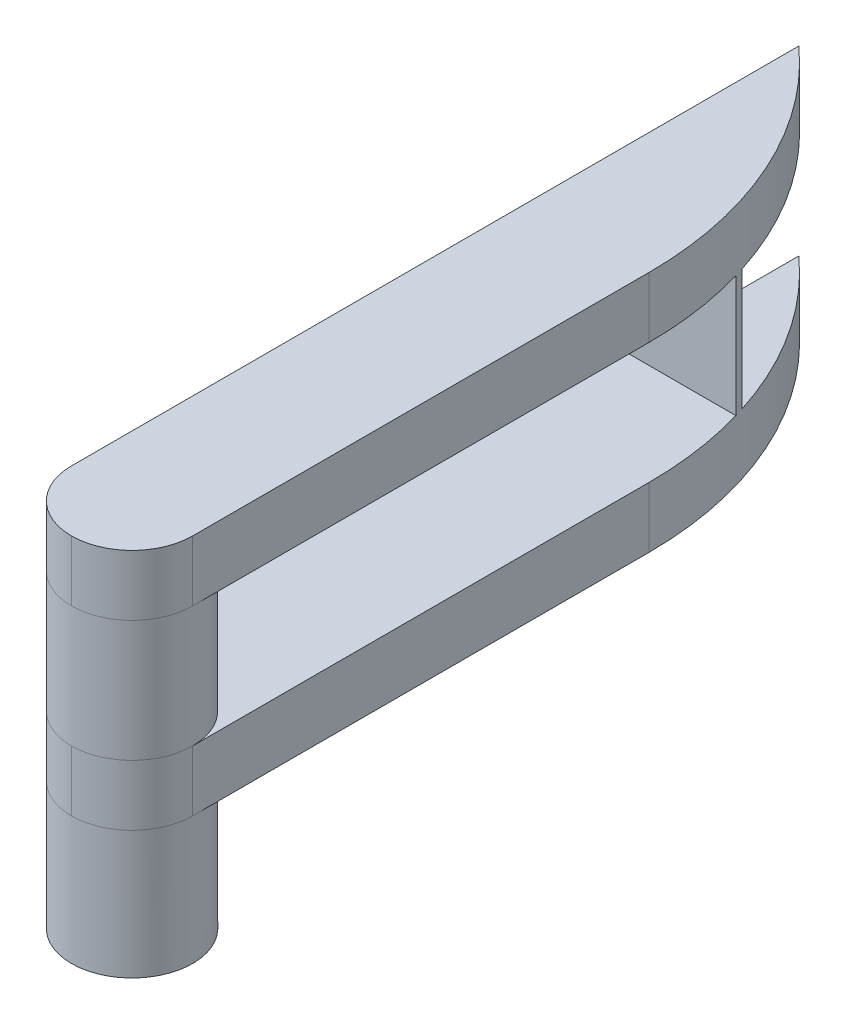
SolidWorks part; units mm, degrees
ref_plane "Plan de face" through (0, 0, 0) normal (0, 0, 1) x (1, 0, 0)
ref_plane "Plan de dessus" through (0, 0, 0) normal (0, 1, 0) x (1, 0, 0)
ref_plane "Plan de droite" through (0, 0, 0) normal (1, 0, 0) x (0, 0, -1)
sketch "Esquisse1" plane through (0, 0, 0) normal (1, 0, 0) x (0, 0, -1)
  line L1 (0, 0) -> (20, 0)
  line L2 (0, 0) -> (0, 5)
  line L3 (0, 5) -> (20, 5)
  line L4 (20, 0) -> (20, 5)
  line L5 (0, 5) -> (10, 5)
  line L6 (0, 5) -> (0, 15)
  line L7 (0, 15) -> (10, 15)
  line L8 (10, 5) -> (10, 15)
  line L9 (0, 15) -> (20, 15)
  line L10 (0, 15) -> (0, 20)
  line L11 (0, 20) -> (20, 20)
  line L12 (20, 15) -> (20, 20)
  line L13 (0, 15) -> (-45, 15)
  line L14 (0, 15) -> (0, 20)
  line L15 (0, 20) -> (-45, 20)
  line L16 (-45, 15) -> (-45, 20)
  line L17 (0, 0) -> (-45, 0)
  line L18 (0, 0) -> (0, 5)
  line L19 (0, 5) -> (-45, 5)
  line L20 (-45, 0) -> (-45, 5)
  dimension "D1" = 10
  dimension "D2" = 5
  dimension "D3" = 5
  dimension "D4" = 5
  dimension "D5" = 5
  dimension "D6" = 10
  dimension "D7" = 20
  dimension "D8" = 20
  dimension "D9" = 45
  dimension "D10" = 45
extrude "Boss.-Extru.2" add sketch "Esquisse1" along normal blind 10 contours L16 L13 L10 L15 | L9 L12 L11 L10 L7 | L20 L17 L2 L19 | L1 L4 L3 L2 region at (0, 2.5, -10) region at (0, 2.5, 22.5) region at (0, 17.5, -10) region at (0, 17.5, 22.5)
sketch "Esquisse2" plane through (0, 15, 0) normal (0, -1, 0) x (1, 0, 0)
  line L11 (0, -6) -> (10, -6)
  line L17 (0, -20) -> (0, 45) construction
  line L18 (10, -20) -> (10, 45) construction
  line L19 (10, -20) -> (0, -20) construction
  line L20 (0, -11) -> (10, -11)
  line L21 (10, -6) -> (0, -11)
  line L22 (0, -6) -> (0, -11)
  line M1 (0, 45) -> (0, -20)
  dimension "D1" = 14
  dimension "D2" = 9
extrude "Boss.-Extru.3" add sketch "Esquisse2" along normal blind 11 contours M1 region at (3.3333, 15, -7.6667)
fillet "Congé1" radius 30 1 edges at (10, 17.5, -20)
fillet "Congé2" radius 30 1 edges at (10, 2.5, -20)
sketch "Esquisse4" plane through (0, 20, 0) normal (0, 1, 0) x (1, 0, 0)
  line L1 (10, -45) -> (0, -45) construction
  line L2 (5, -45) -> (5, -35) construction
  circle A0 centre (5, -40) radius 5
  dimension "D1" = 10
extrude "Boss.-Extru.5" add sketch "Esquisse4" against normal blind 30.55
fillet "Congé4" radius 5 4 edges at (0, 2.5, 45) (10, 2.5, 45) (10, 17.5, 45) (0, 17.5, 45)
